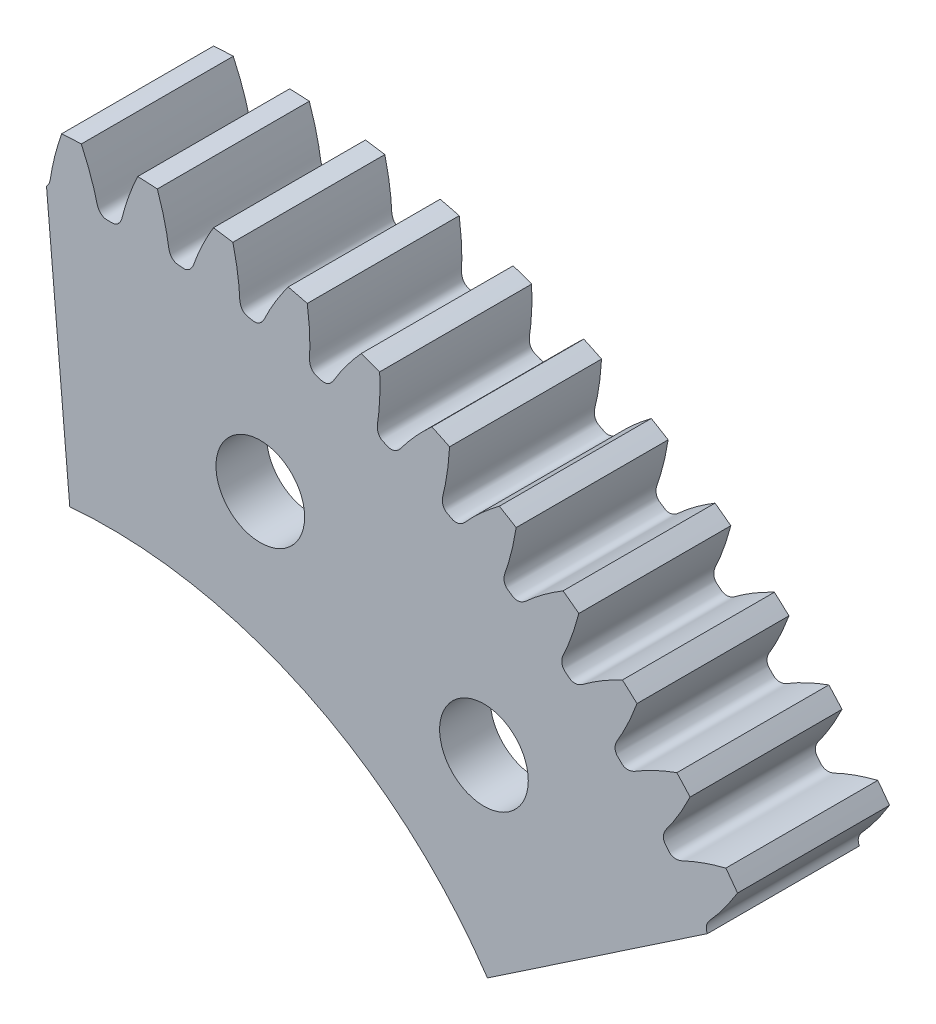
SolidWorks part; units mm, degrees
material "Д16 ГОСТ 4784-97"
ref_plane "FRONT" through (0, 0, 0) normal (0, 0, 1) x (1, 0, 0)
ref_plane "TOP" through (0, 0, 0) normal (0, 1, 0) x (1, 0, 0)
ref_plane "RIGHT" through (0, 0, 0) normal (1, 0, 0) x (0, 0, -1)
ref_axis "Ось1" through (0, 0, 50) along (0, 0, -1)
sketch "SketchRevolveSpurAssemblyNew1Gear" plane through (0, 0, 0) normal (1, 0, 0) x (0, 0, -1)
  line L0 (0, 0) -> (1, 0) construction
  line L1 (-4, 0) -> (-4, 30.5859)
  line L2 (-4, 30.5859) -> (2, 30.5859)
  line L3 (2, 30.5859) -> (2, 0)
  line L4 (2, 0) -> (-4, 0)
  dimension "D1" = 6
revolve "SpurAssemblyNew1Gear" add sketch "SketchRevolveSpurAssemblyNew1Gear" angle 360 about L0
sketch "SketchToothSpurAssemblyNew1Gear" plane through (0, 0, 0) normal (0, 0, 1) x (1, 0, 0)
  arc A0 (30.5945, 1.1268) -> (30.5945, -1.1268) centre (0, 0) cw
  spline S0 degree 3 poles (30.5945, -1.1268) (30.5132, -1.0888) (30.3922, -1.0339) (30.2321, -0.9645) (30.1166, -0.9161) (30.0041, -0.8705) (29.8946, -0.8275) (29.7881, -0.7872) (29.6848, -0.7494) (29.5845, -0.7141) (29.4875, -0.6811) (29.3937, -0.6505) (29.3032, -0.6221) (29.216, -0.5958) (29.1321, -0.5716) (29.0516, -0.5494) (28.953, -0.523) (28.873, -0.505) (28.8129, -0.4861) (28.7913, -0.4788) (28.7701, -0.4709) (28.7493, -0.4625) (28.7287, -0.4535) (28.7084, -0.4437) (28.6882, -0.4331) (28.6681, -0.4215) (28.648, -0.4087) (28.6279, -0.3944) (28.6078, -0.3785) (28.5876, -0.3604) (28.5676, -0.3397) (28.5479, -0.3161) (28.529, -0.289) (28.5115, -0.2581) (28.4964, -0.2233) (28.4848, -0.1848) (28.478, -0.1456) (28.4749, -0.0836) (28.4778, 0) (28.4749, 0.0836) (28.478, 0.1456) (28.4848, 0.1848) (28.4964, 0.2233) (28.5115, 0.2581) (28.529, 0.289) (28.5479, 0.3161) (28.5676, 0.3397) (28.5876, 0.3604) (28.6078, 0.3785) (28.6279, 0.3944) (28.648, 0.4087) (28.6681, 0.4215) (28.6882, 0.4331) (28.7084, 0.4437) (28.7287, 0.4535) (28.7493, 0.4625) (28.7701, 0.4709) (28.7913, 0.4788) (28.8129, 0.4861) (28.873, 0.505) (28.953, 0.523) (29.0516, 0.5494) (29.1321, 0.5716) (29.216, 0.5958) (29.3032, 0.6221) (29.3937, 0.6505) (29.4875, 0.6811) (29.5845, 0.7141) (29.6848, 0.7494) (29.7881, 0.7872) (29.8946, 0.8275) (30.0041, 0.8705) (30.1166, 0.9161) (30.2321, 0.9645) (30.3922, 1.0339) (30.5132, 1.0888) (30.5945, 1.1268) knots 0 0 0 0 0.052869 0.078188 0.102762 0.126592 0.149678 0.172019 0.193617 0.21447 0.234579 0.253943 0.272564 0.29044 0.307572 0.32396 0.339603 0.367681 0.372205 0.376674 0.381103 0.385507 0.389906 0.394324 0.398788 0.403329 0.407986 0.412802 0.417828 0.423121 0.428742 0.434755 0.441216 0.448165 0.45561 0.463513 0.471776 0.478976 0.5 0.521024 0.528224 0.536487 0.54439 0.551835 0.558784 0.565245 0.571258 0.576879 0.582172 0.587198 0.592014 0.596671 0.601212 0.605676 0.610094 0.614493 0.618897 0.623326 0.627795 0.632319 0.660397 0.67604 0.692428 0.70956 0.727436 0.746057 0.765421 0.78553 0.806383 0.827981 0.850322 0.873408 0.897238 0.921812 0.947131 1 1 1 1
extrude "ToothExtrudeCutSpurAssemblyNew1Gear" cut sketch "SketchToothSpurAssemblyNew1Gear" against normal blind 4 and the other way blind 4
pattern_circular "PatternSpurAssemblyNew1Gear" count 64 every 5.625 about axis through (0, 0, 50) along (0, 0, -1) of "ToothExtrudeCutSpurAssemblyNew1Gear"
sketch "AuxiliarySketchSpurAssemblyNew1Gear" plane through (0, 0, 0) normal (0, 0, 1) x (1, 0, 0)
  circle A0 centre (0, 0) radius 30 construction
  circle A1 centre (0, 0) radius 28.1908 construction
  circle A2 centre (0, 0) radius 28.8965 construction
  circle A3 centre (0, 0) radius 30.5859 construction
  circle A4 centre (0, 0) radius 28.4766 construction
  dimension "PitchDiameter" = 60
  dimension "BaseDiameter" = 56.3816
  dimension "FormDiameter" = 57.7931
  dimension "MajorDiameter" = 61.1719
  dimension "MinorDiameter" = 56.9531
sketch "Эскиз1" plane through (0, 0, 4) normal (0, 0, 1) x (1, 0, 0)
  line L0 (0, 0) -> (-3.3338, 38.1056) construction
  line L1 (0, 0) -> (31.7117, 21.3898) construction
  line L2 (0, 0) -> (10.2369, 38.2045) construction
  line L3 (0, 0) -> (25.0803, 29.8895) construction
  line L4 (-1.5688, 17.9315) -> (-3.3338, 38.1056)
  line L5 (14.9227, 10.0655) -> (31.7117, 21.3898)
  line L6 (0, 0) -> (0, 44.5012) construction
  arc A0 (-3.3338, 38.1056) -> (31.7117, 21.3898) centre (0, 0) ccw
  circle A1 centre (0, 0) radius 23 construction
  circle A2 centre (5.9528, 22.2163) radius 1.75
  circle A3 centre (14.7841, 17.619) radius 1.75
  arc A4 (14.9227, 10.0655) -> (-1.5688, 17.9315) centre (0, 0) ccw
  dimension "D1" = 61
  dimension "D2" = 15
  dimension "D3" = 25
  dimension "D4" = 3.5
  dimension "D5" = 3.5
  dimension "D6" = 46
  dimension "D7" = 18
  dimension "D8" = 5
extrude "Вырез-Вытянуть1" cut sketch "Эскиз1" against normal through all
sketch "Эскиз2" plane through (0, 0, -2) normal (0, 0, 1) x (1, 0, 0)
  circle A0 centre (0, 0) radius 26.5
  dimension "D1" = 53
extrude "Вырез-Вытянуть2" cut sketch "Эскиз2" along normal blind 4
